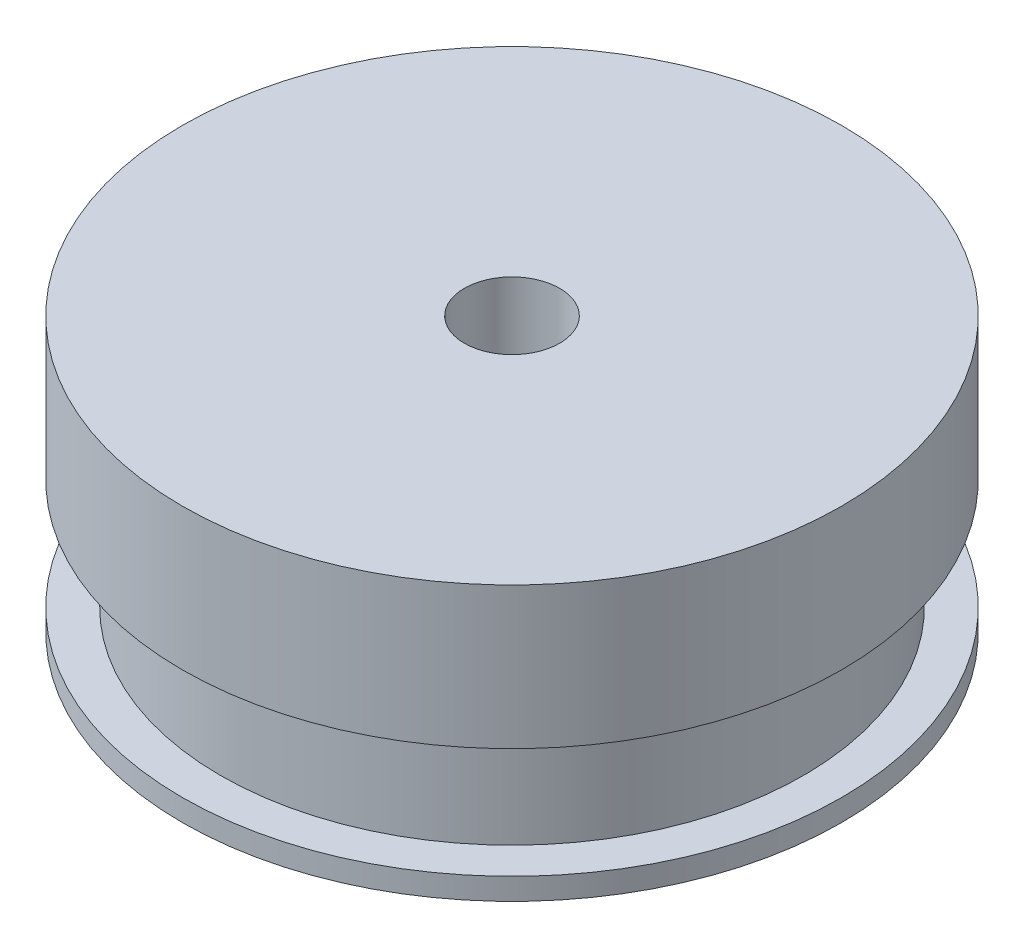
SolidWorks part; units mm, degrees
ref_plane "Front Plane" through (0, 0, 0) normal (0, 0, 1) x (1, 0, 0)
ref_plane "Top Plane" through (0, 0, 0) normal (0, 1, 0) x (1, 0, 0)
ref_plane "Right Plane" through (0, 0, 0) normal (1, 0, 0) x (0, 0, -1)
sketch "Sketch1" plane through (0, 0, 0) normal (0, 1, 0) x (1, 0, 0)
  circle A0 centre (0, 0) radius 21.971
  circle A1 centre (0, 0) radius 3.175
  dimension "D1" = 43.942
  dimension "D2" = 6.35
extrude "Boss-Extrude1" add sketch "Sketch1" along normal blind 18.2626
ref_axis "Axis1" through (0, 18.2626, 0) along (0, -1, 0)
sketch "Sketch2" plane through (0, 0, 0) normal (1, 0, 0) x (0, 0, -1)
  line L0 (21.971, 1.4478) -> (19.431, 1.4478)
  line L1 (19.431, 1.4478) -> (19.431, 8.8138)
  line L2 (19.431, 8.8138) -> (21.971, 8.8138)
  line L3 (21.971, 0) -> (21.971, 18.2626) construction
  line L4 (21.971, 8.8138) -> (21.971, 1.4478)
  line L5 (-21.971, 0) -> (21.971, 0) construction
  dimension "D1" = 7.366
  dimension "D2" = 2.54
  dimension "D3" = 1.4478
revolve "Cut-Revolve1" cut sketch "Sketch2" angle 360 about axis through (0, 18.2626, 0) along (0, -1, 0)
